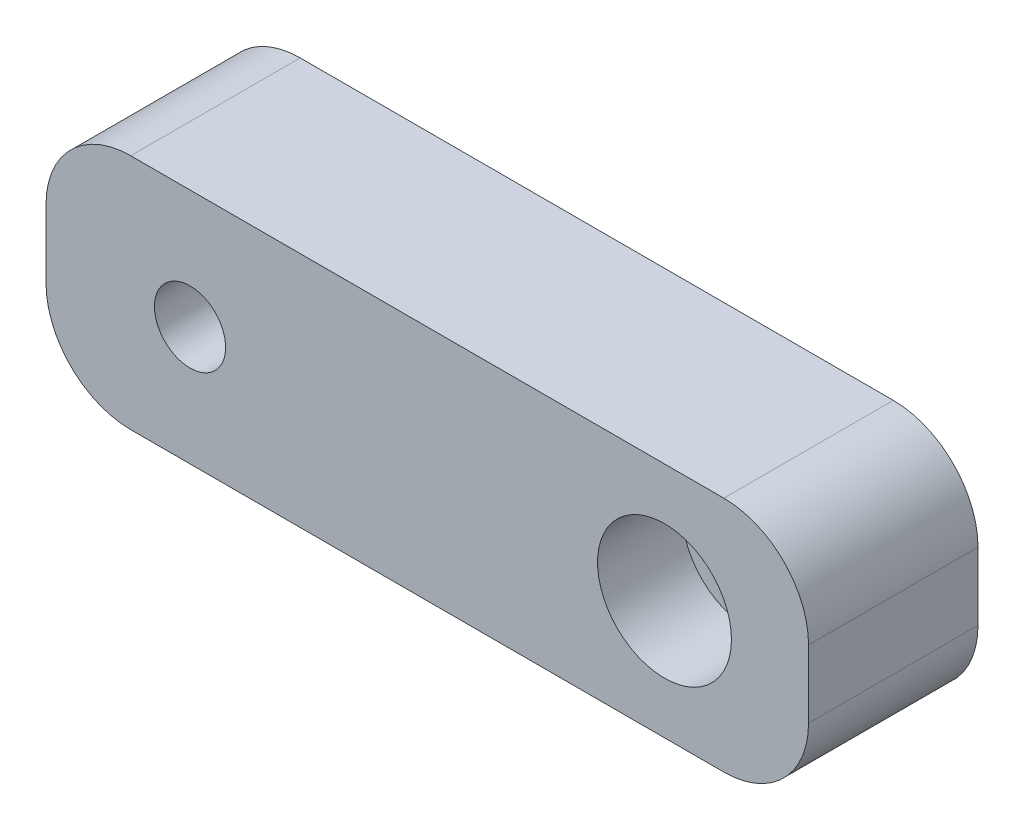
SolidWorks part; units mm, degrees
ref_plane "Front Plane" through (0, 0, 0) normal (0, 0, 1) x (1, 0, 0)
ref_plane "Top Plane" through (0, 0, 0) normal (0, 1, 0) x (1, 0, 0)
ref_plane "Right Plane" through (0, 0, 0) normal (1, 0, 0) x (0, 0, -1)
sketch "Sketch1" plane through (0, 0, 0) normal (0, 0, 1) x (1, 0, 0)
  line L1 (-59.3506, 20.3019) -> (-14.3506, 20.3019)
  line L2 (-59.3506, 20.3019) -> (-59.3506, 6.3019)
  line L3 (-59.3506, 6.3019) -> (-14.3506, 6.3019)
  line L4 (-14.3506, 20.3019) -> (-14.3506, 6.3019)
extrude "Boss-Extrude1" add sketch "Sketch1" along normal blind 10 contours L1 L4 L3 L2
fillet "Fillet1" radius 5 1 edges at (-59.3506, 20.3019, 5)
fillet "Fillet2" radius 5 3 edges at (-14.3506, 6.3019, 5) (-14.3506, 20.3019, 5) (-59.3506, 6.3019, 5)
sketch "Sketch2" plane through (0, 0, 0) normal (0, 0, -1) x (-1, 0, 0)
  line L0 (59.3506, 15.3019) -> (59.3506, 11.3019) construction
  line L1 (54.3506, 20.3019) -> (19.3506, 20.3019) construction
  circle A0 centre (50.8506, 13.3019) radius 4
  point P4 (59.3506, 13.3019)
  dimension "D1" = 8.5
  dimension "D2" = 7
extrude "Cut-Extrude2" cut sketch "Sketch2" against normal blind 2.5 contours A0
sketch "Sketch3" plane through (0, 0, 2.5) normal (0, 0, -1) x (-1, 0, 0)
  circle A2 centre (50.8506, 13.3019) radius 2.1
extrude "Cut-Extrude3" cut sketch "Sketch3" against normal blind 2 contours A2
sketch "Sketch4" plane through (0, 0, 10) normal (0, 0, 1) x (1, 0, 0)
  line L0 (-14.3506, 15.3019) -> (-14.3506, 11.3019) construction
  line L1 (-54.3506, 20.3019) -> (-19.3506, 20.3019) construction
  circle A0 centre (-22.8506, 13.3019) radius 3.95
  dimension "D1" = 8.5
  dimension "D2" = 7
extrude "Cut-Extrude4" cut sketch "Sketch4" against normal blind 5 contours A0
sketch "Sketch5" plane through (0, 0, 5) normal (0, 0, 1) x (1, 0, 0)
  circle A0 centre (-22.8506, 13.3019) radius 2
extrude "Cut-Extrude5" cut sketch "Sketch5" against normal up to next contours A0
sketch "Sketch6" plane through (0, 0, 0) normal (0, 0, -1) x (-1, 0, 0)
  circle A0 centre (22.8506, 13.3019) radius 2.1
  circle A1 centre (22.8506, 13.3019) radius 3.5
sketch "Sketch7" plane through (0, 0, 4.5) normal (0, 0, -1) x (-1, 0, 0)
  circle A0 centre (50.8506, 13.3019) radius 2.1
extrude "Cut-Extrude6" cut sketch "Sketch7" against normal through all
